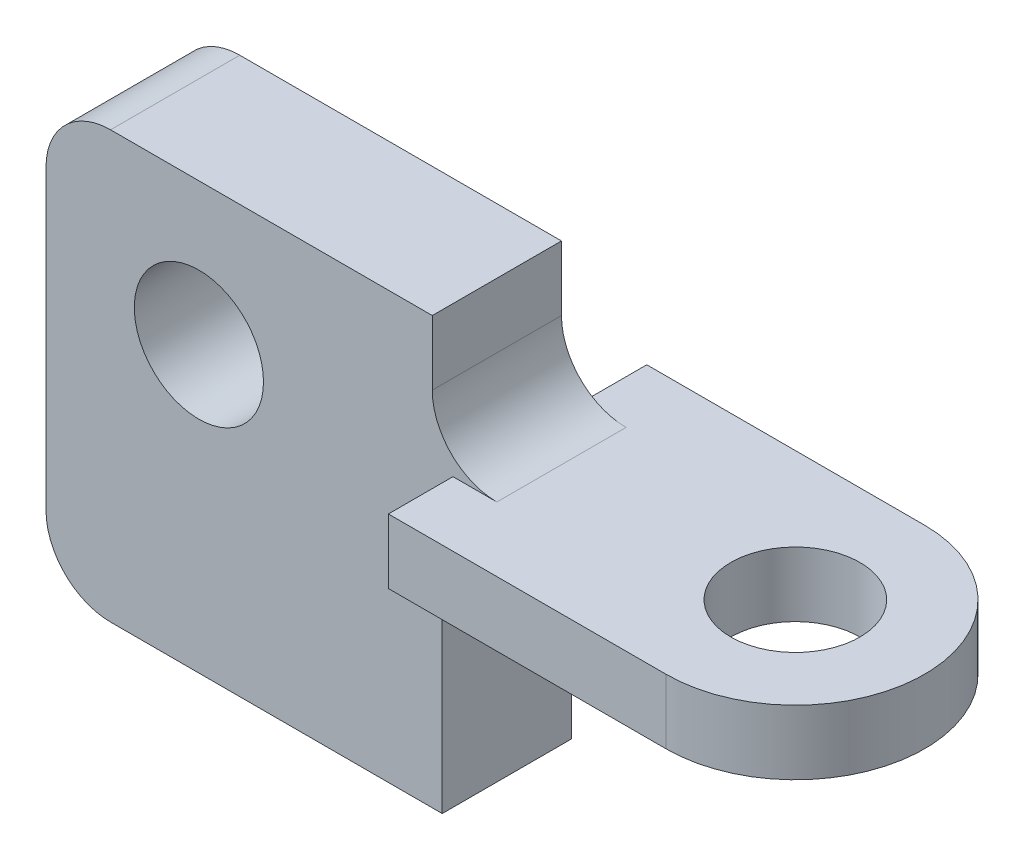
SolidWorks part; units mm, degrees
ref_plane "Front Plane" through (0, 0, 0) normal (0, 0, 1) x (1, 0, 0)
ref_plane "Top Plane" through (0, 0, 0) normal (0, 1, 0) x (1, 0, 0)
ref_plane "Right Plane" through (0, 0, 0) normal (1, 0, 0) x (0, 0, -1)
sketch "Sketch1" plane through (0, 0, 0) normal (0, 1, 0) x (1, 0, 0)
  line L0 (0, 0) -> (1772.8058, 0) construction
  line L1 (0, -254) -> (0, 254)
  line L2 (0, 254) -> (1772.8058, 254)
  line L3 (0, -254) -> (1772.8058, -254)
  line L4 (1772.8058, 254) -> (1772.8058, -254)
  line L5 (1600.2, 254) -> (1600.2, 508)
  line L6 (1600.2, -254) -> (1600.2, -508)
  line L7 (1600.2, 508) -> (2692.4, 508)
  line L8 (1600.2, -508) -> (2692.4, -508)
  arc A0 (2692.4, 508) -> (2692.4, -508) centre (2692.4, 0) cw
  circle A1 centre (2692.4, 0) radius 254
  dimension "D2" = 508
  dimension "D3" = 508
  dimension "D1" = 1600.2
  dimension "D4" = 508
  dimension "D5" = 1092.2
extrude "Boss-Extrude1" add sketch "Sketch1" along normal blind 508 and the other way blind 914.4 contours L1 L0 L4 L2 | L0 L1 L3 L4 region at (886.4029, 0, -127) region at (886.4029, 0, 127)
extrude "Boss-Extrude2" add sketch "Sketch1<3>" along normal blind 254 contours A0 L7 L5 L2 L4 L3 L6 L8 A1 region at (2340.9637, 0, 0)
sketch "Sketch1<3>" plane through (0, 0, 0) normal (0, 1, 0) x (1, 0, 0) same geometry as "Sketch1"
extrude "Boss-Extrude3" add sketch "Sketch1<4>" along normal blind 762 contours L1 L0 L4 L2 | L0 L1 L3 L4 region at (886.4029, 0, -127) region at (886.4029, 0, 127)
sketch "Sketch1<4>" plane through (0, 0, 0) normal (0, 1, 0) x (1, 0, 0) same geometry as "Sketch1"
sketch "Sketch11" plane through (0, 0, 254) normal (0, 0, 1) x (1, 0, 0)
  line L0 (1772.8058, 254) -> (1772.8058, 762) construction
  line L1 (1518.8058, 508) -> (1518.8058, 762)
  line L2 (0, 762) -> (1772.8058, 762) construction
  line L3 (1772.8058, -914.4) -> (1772.8058, 0) construction
  line L4 (1557.9486, -214.8573) -> (1557.9486, -914.4)
  line L5 (0, -914.4) -> (1772.8058, -914.4) construction
  line L6 (1518.8058, 762) -> (1772.8058, 762)
  line L7 (1772.8058, 762) -> (1772.8058, 254)
  line L8 (1772.8058, 0) -> (1772.8058, -914.4)
  line L9 (1772.8058, -914.4) -> (1557.9486, -914.4)
  arc A0 (1772.8058, 254) -> (1518.8058, 508) centre (1772.8058, 508) cw
  arc A1 (1772.8058, 0) -> (1557.9486, -214.8573) centre (1772.8058, -214.8573) ccw
extrude "Cut-Extrude1" cut sketch "Sketch11" against normal blind 608.2608
fillet "Fillet2" radius 254 1 edges at (0, 762, 0)
fillet "Fillet3" radius 254 1 edges at (0, -914.4, 0)
sketch "Sketch12" plane through (0, 0, 254) normal (0, 0, 1) x (1, 0, 0)
  circle A0 centre (601.1292, 204.05) radius 254
extrude "Cut-Extrude2" cut sketch "Sketch12" against normal blind 614.68
